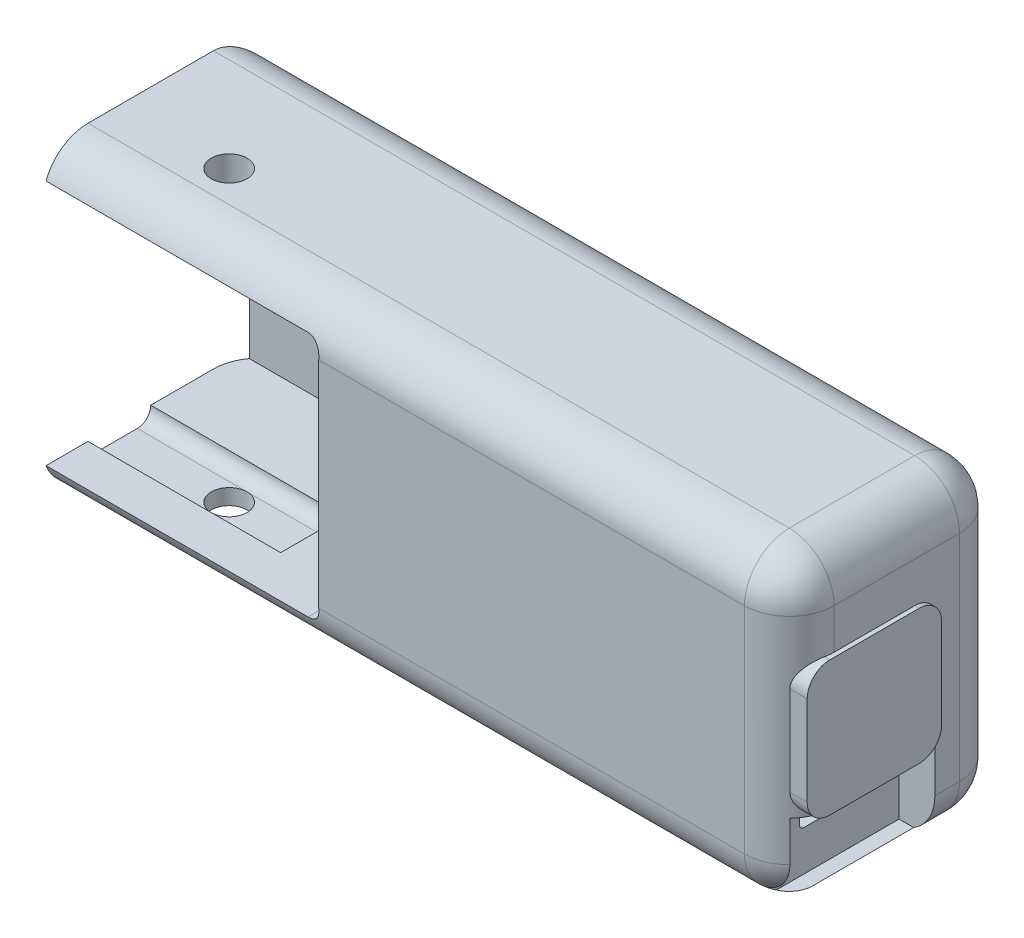
SolidWorks part; units mm, degrees
ref_plane "Front Plane" through (0, 0, 0) normal (0, 0, 1) x (1, 0, 0)
ref_plane "Top Plane" through (0, 0, 0) normal (0, 1, 0) x (1, 0, 0)
ref_plane "Right Plane" through (0, 0, 0) normal (1, 0, 0) x (0, 0, -1)
sketch "Sketch1" plane through (0, 0, 0) normal (0, 1, 0) x (1, 0, 0)
  line L1 (0, 0) -> (166.5, 0)
  line L2 (0, 0) -> (0, 48)
  line L3 (0, 48) -> (166.5, 48)
  line L4 (166.5, 0) -> (166.5, 48)
  dimension "D1" = 166.5
  dimension "D2" = 48
extrude "Boss-Extrude1" add sketch "Sketch1" along normal blind 68
sketch "Sketch2" plane through (0, 0, 0) normal (-1, 0, 0) x (0, 0, 1)
  line L1 (-44, 61.5) -> (0, 61.5)
  line L2 (-44, 61.5) -> (-44, 6.5)
  line L3 (-44, 6.5) -> (0, 6.5)
  line L4 (0, 61.5) -> (0, 6.5)
  line L6 (-48, 68) -> (0, 68) construction
  line L7 (0, 68) -> (0, 0) construction
  line L8 (-48, 68) -> (-48, 0) construction
  point P4 (0, 34)
  point P7 (0, 34)
  dimension "D1" = 4
  dimension "D3" = 6.5
extrude "Cut-Extrude1" cut sketch "Sketch2" against normal blind 61.5
sketch "Sketch3" plane through (61.5, 0, 0) normal (-1, 0, 0) x (0, 0, 1)
  line L0 (-44, 61.5) -> (-44, 6.5) construction
  line L1 (-36.5, 59) -> (-5.5, 59)
  line L2 (-36.5, 59) -> (-36.5, 9)
  line L3 (-36.5, 9) -> (-5.5, 9)
  line L4 (-5.5, 59) -> (-5.5, 9)
  line L5 (0, 61.5) -> (-44, 61.5) construction
  line L6 (0, 6.5) -> (0, 61.5) construction
  line L7 (-44, 6.5) -> (0, 6.5) construction
  point P12 (-21, 9)
  dimension "D1" = 7.5
  dimension "D2" = 2.5
  dimension "D3" = 5.5
  dimension "D4" = 2.5
extrude "Cut-Extrude3" cut sketch "Sketch3" against normal blind 73.5 contours L4 L3 L2 L1
sketch "Sketch4" plane through (0, 0, 0) normal (-1, 0, 0) x (0, 0, 1)
  line L0 (0, 6.5) -> (0, 0) construction
  line L1 (-24, 6.5) -> (-10, 6.5)
  line L2 (-24, 6.5) -> (-24, 3.5)
  line L3 (-24, 3.5) -> (-10, 3.5)
  line L4 (-10, 6.5) -> (-10, 3.5)
  line L5 (-44, 6.5) -> (0, 6.5) construction
  point P6 (-17, 6.5)
  point P9 (-22, 6.5)
  dimension "D1" = 3
  dimension "D2" = 14
  dimension "D3" = 10
extrude "Cut-Extrude4" cut sketch "Sketch4" against normal blind 43
sketch "Sketch5" plane through (0, 68, 0) normal (0, 1, 0) x (1, 0, 0)
  line L1 (166.5, 48) -> (0, 48) construction
  line L2 (0, 48) -> (0, 0) construction
  circle A0 centre (24.5, 17) radius 4
  dimension "D1" = 8
  dimension "D2" = 31
  dimension "D3" = 24.5
extrude "Cut-Extrude5" cut sketch "Sketch5" against normal through all
fillet "Fillet1" radius 10 17 edges at (166.5, 0, -24) (166.5, 34, -48) (166.5, 34, 0) (166.5, 68, -24) (135, 34, -5.5) (135, 34, -36.5) (135, 59, -21) (98.25, 9, -5.5) (98.25, 9, -36.5) (83.25, 0, 0) (0, 34, -48) (83.25, 0, -48) (83.25, 68, -48) (83.25, 68, 0) (98.25, 59, -5.5) (98.25, 59, -36.5) (135, 9, -21)
fillet "Fillet2" radius 3 6 edges at (61.5, 6.5, -22.3163) (61.5, 61.5, -22.3163) (43, 3.5, -17) (21.5, 3.5, -10) (21.5, 3.5, -24) (61.5, 34, -44)
sketch "Sketch6" plane through (166.5, 0, 0) normal (1, 0, 0) x (0, 0, -1)
  line L0 (38, 0) -> (10, 0) construction
  line L1 (3, 19) -> (32.5, 19)
  line L2 (3, 19) -> (3, 1.5)
  line L3 (3, 1.5) -> (32.5, 1.5)
  line L4 (32.5, 19) -> (32.5, 1.5)
  line L5 (0, 10) -> (0, 58) construction
  dimension "D1" = 1.5
  dimension "D2" = 17.5
  dimension "D3" = 29.5
  dimension "D4" = 3
extrude "Cut-Extrude6" cut sketch "Sketch6" against normal blind 8
sketch "Sketch7" plane through (158.5, 0, 0) normal (1, 0, 0) x (0, 0, -1)
  line L0 (3, 19) -> (3, 10) construction
  line L1 (10.25, 19) -> (31.75, 19)
  line L2 (10.25, 19) -> (10.25, 10.5)
  line L3 (10.25, 10.5) -> (31.75, 10.5)
  line L4 (31.75, 19) -> (31.75, 10.5)
  line L7 (32.5, 19) -> (3, 19) construction
  point P8 (21, 19)
  point P9 (17.75, 19)
  dimension "D1" = 8.5
  dimension "D2" = 7.25
  dimension "21.5" = 21.5
extrude "Cut-Extrude16" cut sketch "Sketch7" against normal through all
sketch "Sketch8" plane through (166.5, 0, 0) normal (1, 0, 0) x (0, 0, -1)
  line L1 (3, 49) -> (33, 49)
  line L2 (3, 49) -> (3, 19)
  line L3 (3, 19) -> (33, 19)
  line L4 (33, 49) -> (33, 19)
  dimension "D1" = 30
  dimension "D2" = 30
extrude "Boss-Extrude2" add sketch "Sketch8" along normal blind 1 and the other way blind 3
fillet "Fillet3" radius 5 4 edges at (165.5707, 19, -3) (165.5707, 49, -3) (167, 49, -33) (167, 19, -33)
fillet "Fillet4" radius 1 3 edges at (141.9665, 10.5, -31.75) (141.9665, 10.5, -10.25) (146.0055, 19, -10.25)
